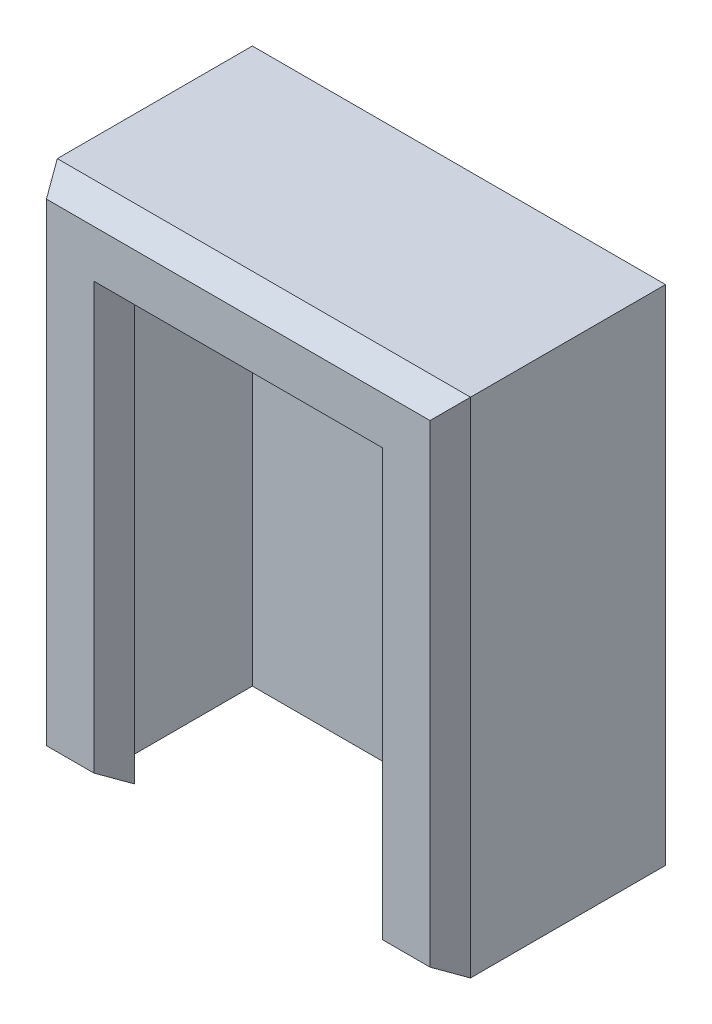
SolidWorks part; units mm, degrees
ref_plane "Plano frontal" through (0, 0, 0) normal (0, 0, 1) x (1, 0, 0)
ref_plane "Plano superior" through (0, 0, 0) normal (0, 1, 0) x (1, 0, 0)
ref_plane "Plano direito" through (0, 0, 0) normal (1, 0, 0) x (0, 0, -1)
sketch "Esboço1" plane through (0, 0, 0) normal (0, 0, 1) x (1, 0, 0)
  line L0 (0, -2) -> (0, 15.6)
  line L1 (0, 15.6) -> (-12.1, 15.6)
  line L2 (-12.1, 15.6) -> (-12.1, -2)
  line L3 (-12.1, 0) -> (0, 0)
  line L4 (-14.1, -2) -> (2, -2)
  line L5 (2, -2) -> (2, 17.6)
  line L6 (2, 17.6) -> (-14.1, 17.6)
  line L7 (-14.1, 17.6) -> (-14.1, -2)
  line L8 (0, 0) -> (0, 15.6) construction
  line L9 (-12.1, 15.6) -> (-12.1, 0) construction
  dimension "D1" = 2
extrude "Ressalto-extrusão1" add sketch "Esboço1" along normal blind 5.6 contours L6 L7 L4 L2 L1 L0 L5 region at (0.2536, -1, 0)
extrude "Ressalto-extrusão2" add sketch "Esboço1<3>" against normal blind 2 contours L6 L7 L4 L2 L1 L0 L5 | L2 L3 L0 L1 | L2 L4 L0 L3 region at (-6.05, -1, 0) region at (0.2536, -1, 0) region at (-6.05, 7.8, 0)
sketch "Esboço1<3>" plane through (0, 0, 0) normal (0, 0, 1) x (1, 0, 0) same geometry as "Esboço1"
sketch "Esboço2" plane through (0, 0, 5.6) normal (0, 0, 1) x (1, 0, 0)
  line L5 (-11.1, 14.6) -> (-11.1, -2)
  line L6 (-14.1, 17.6) -> (2, 17.6)
  line L7 (-14.1, 17.6) -> (-14.1, -2)
  line L8 (-14.1, -2) -> (2, -2)
  line L9 (2, 17.6) -> (2, -2)
  line L11 (-1, 14.6) -> (-1, -2)
  line L12 (-11.1, 14.6) -> (-1, 14.6)
  line L13 (-11.1, 14.6) -> (-11.1, 1) construction
  line L14 (-1, 14.6) -> (-1, 1) construction
  line L15 (-11.1, 1) -> (-1, 1) construction
  line M9 (2, 17.6) -> (-14.1, 17.6)
  line M10 (-14.1, 17.6) -> (-14.1, -2)
  line M11 (-14.1, -2) -> (-12.1, -2)
  line M12 (-12.1, -2) -> (-12.1, 15.6)
  line M13 (-12.1, 15.6) -> (0, 15.6)
  line M14 (0, 15.6) -> (0, -2)
  line M15 (0, -2) -> (2, -2)
  line M16 (2, -2) -> (2, 17.6)
  dimension "D1" = 3
extrude "Ressalto-extrusão3" add sketch "Esboço2" along normal blind 1 draft 30 contours M16 M9 M10 M11 M12 M13 M14 M15 | L5 L12 L11 L8 M14 M13 M12 region at (-11.3136, 6.3, 5.6) region at (-13.1, -1.7464, 5.6)
